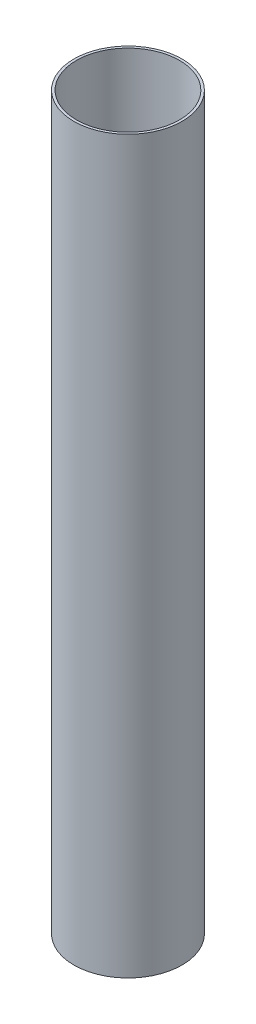
SolidWorks part; units mm, degrees
material "A-Glass Fiber"
ref_plane "Front Plane" through (0, 0, 0) normal (0, 0, 1) x (1, 0, 0)
ref_plane "Top Plane" through (0, 0, 0) normal (0, 1, 0) x (1, 0, 0)
ref_plane "Right Plane" through (0, 0, 0) normal (1, 0, 0) x (0, 0, -1)
sketch "Sketch1" plane through (0, 0, 0) normal (0, 1, 0) x (1, 0, 0)
  circle A0 centre (0, 0) radius 49.55
  circle A1 centre (0, 0) radius 51.95
  dimension "D1" = 99.1
  dimension "D2" = 2.4
extrude "Boss-Extrude1" add sketch "Sketch1" along normal blind 351 and the other way blind 351
